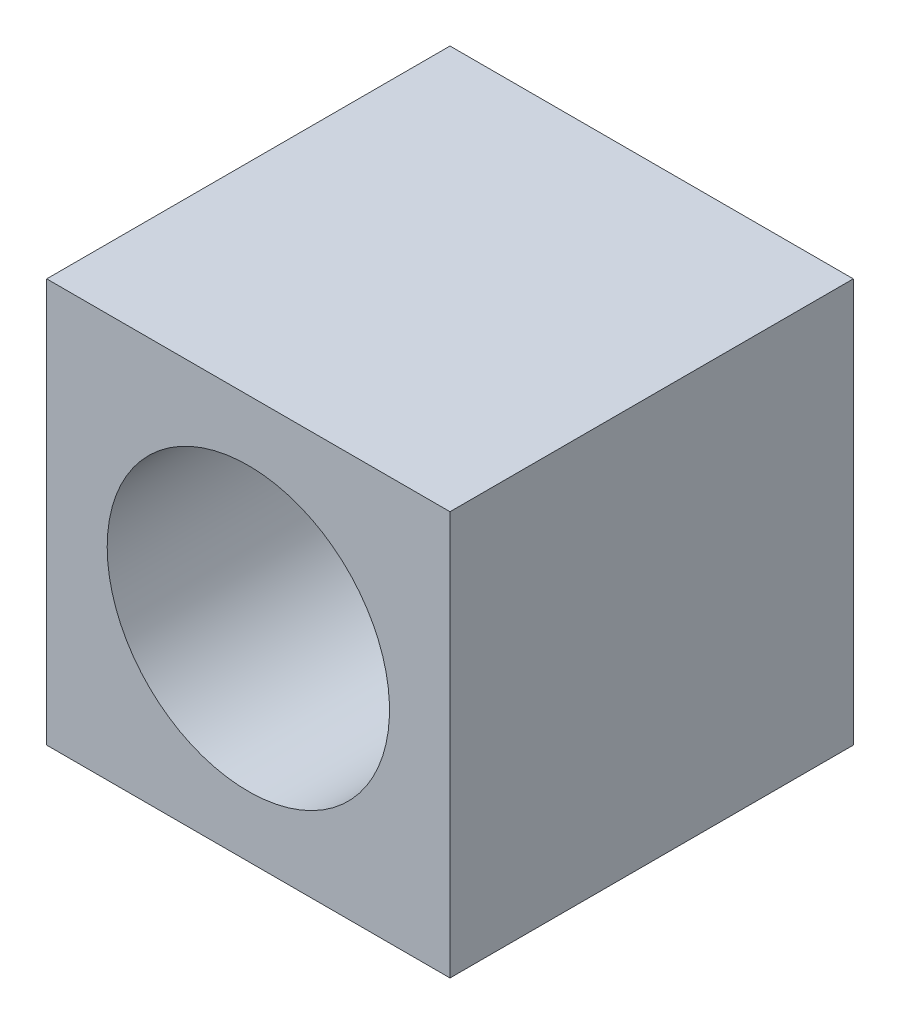
SolidWorks part; units mm, degrees
material "Plain Carbon Steel"
ref_plane "Front Plane" through (0, 0, 0) normal (0, 0, 1) x (1, 0, 0)
ref_plane "Top Plane" through (0, 0, 0) normal (0, 1, 0) x (1, 0, 0)
ref_plane "Right Plane" through (0, 0, 0) normal (1, 0, 0) x (0, 0, -1)
sketch "Sketch1" plane through (0, 0, 0) normal (0, 0, 1) x (1, 0, 0)
  line L1 (-19.05, -19.075) -> (19.05, -19.075)
  line L2 (-19.05, -19.075) -> (-19.05, 19.075)
  line L3 (-19.05, 19.075) -> (19.05, 19.075)
  line L4 (19.05, -19.075) -> (19.05, 19.075)
  line L5 (-19.05, -19.075) -> (19.05, 19.075) construction
  line L6 (-19.05, 19.075) -> (19.05, -19.075) construction
  circle A0 centre (0, 0) radius 13.335
  dimension "D1" = 38.1
  dimension "D2" = 26.67
extrude "Boss-Extrude1" add sketch "Sketch1" along normal blind 38.1
ref_axis "Axis1" through (0, 0, 38.1) along (0, 0, -1)
